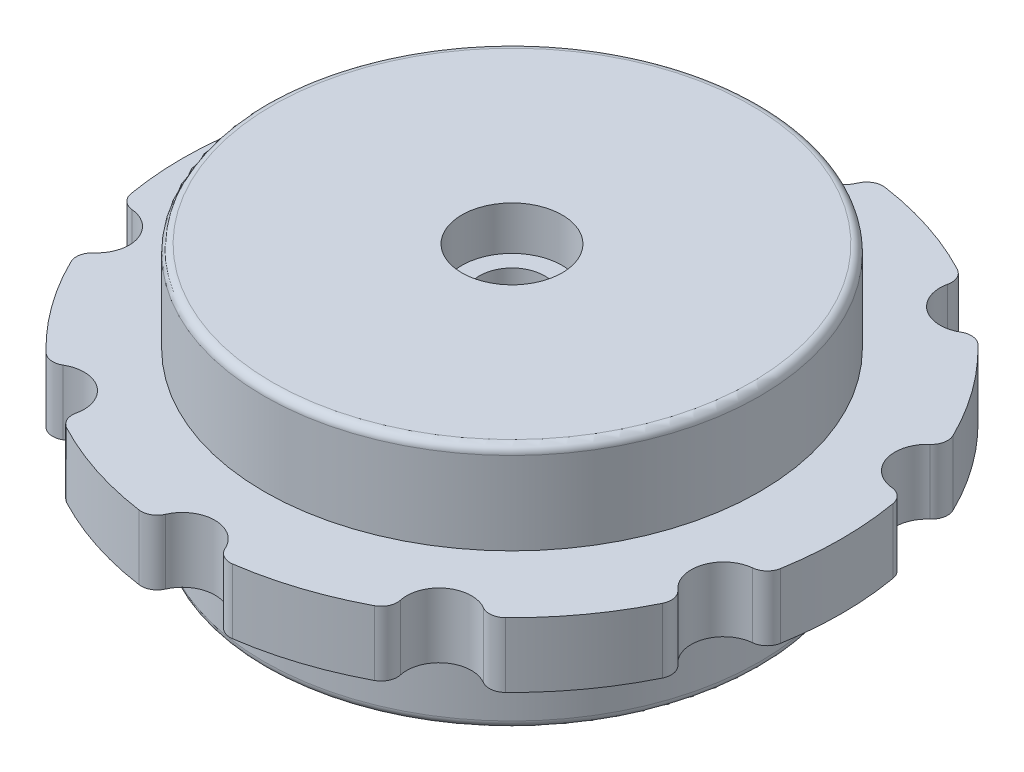
SolidWorks part; units mm, degrees
ref_plane "前视基准面" through (0, 0, 0) normal (0, 0, 1) x (1, 0, 0)
ref_plane "上视基准面" through (0, 0, 0) normal (0, 1, 0) x (1, 0, 0)
ref_plane "右视基准面" through (0, 0, 0) normal (1, 0, 0) x (0, 0, -1)
other "Configuration Table"
sketch "草图1" plane through (0, 0, 0) normal (0, 1, 0) x (1, 0, 0)
  circle A0 centre (0, 0) radius 15.3
  circle A1 centre (0, 0) radius 20.35
  circle A2 centre (0, 0) radius 13.7
  circle A3 centre (0, 20.35) radius 2
  dimension "D1" = 30.6
  dimension "D2" = 40.7
  dimension "D3" = 1.6
  dimension "D4" = 4
extrude "凸台-拉伸1" add sketch "草图1" along normal mid plane 15.2 contours A0 | A2
extrude "凸台-拉伸2" add sketch "草图1<3>" along normal mid plane 4 contours A1
sketch "草图1<3>" plane through (0, 0, 0) normal (0, 1, 0) x (1, 0, 0) same geometry as "草图1"
extrude "切除-拉伸1" cut sketch "草图1<4>" against normal through all both and the other way through all contours A3
sketch "草图1<4>" plane through (0, 0, 0) normal (0, 1, 0) x (1, 0, 0) same geometry as "草图1"
fillet "圆角1" radius 1 2 edges at (1.9976, 0, -20.2517) (-1.9976, 0, -20.2517)
pattern_circular "阵列(圆周)1" count 10 over 360 about axis through (0, 2, 0) along (0, -1, 0) of "切除-拉伸1", "圆角1"
fillet "圆角2" radius 0.5 2 edges at (0, -7.6, 15.3) (0, 7.6, 15.3)
extrude "凸台-拉伸3" add sketch "草图1<5>" along normal mid plane 7.8 contours A2
sketch "草图1<5>" plane through (0, 0, 0) normal (0, 1, 0) x (1, 0, 0) same geometry as "草图1"
extrude "凸台-拉伸5" add sketch "草图1<6>" along normal up to surface (7.6 mm away) from surface contours A2 up to face at (0, 7.6, 14.8) starting at face at (0, -7.6, 14.8)
sketch "草图1<6>" plane through (0, 0, 0) normal (0, 1, 0) x (1, 0, 0) same geometry as "草图1"
sketch "草图2" plane through (0, 2, 0) normal (0, 1, 0) x (1, 0, 0)
  line L0 (0, 20.35) -> (11.9614, 16.4635)
  line L1 (-11.9614, 16.4635) -> (0, 20.35)
  arc A0 (-1.834, 19.5523) -> (1.834, 19.5523) centre (0, 20.35) ccw construction
  arc A1 (10.0088, 16.8962) -> (12.9763, 14.7401) centre (11.9614, 16.4635) ccw construction
  arc A2 (-12.9763, 14.7401) -> (-10.0088, 16.8962) centre (-11.9614, 16.4635) ccw construction
  dimension "D1" = 12.577
  dimension "D2" = 12.577
sketch "草图4" plane through (0, -7.6, 0) normal (0, -1, 0) x (1, 0, 0)
  circle A0 centre (0, 0) radius 2
  circle A1 centre (0, 0) radius 3.1
  dimension "D1" = 4
  dimension "D2" = 6.2
extrude "切除-拉伸3" cut sketch "草图4" against normal through all contours A0
extrude "切除-拉伸4" cut sketch "草图4<3>" against normal blind 2.7 contours A1
sketch "草图4<3>" plane through (0, -7.6, 0) normal (0, -1, 0) x (1, 0, 0) same geometry as "草图4"
extrude "切除-拉伸5" cut sketch "草图4<4>" along normal blind 2.7 from surface contours A1 starting at face at (0, 7.6, -2)
sketch "草图4<4>" plane through (0, -7.6, 0) normal (0, -1, 0) x (1, 0, 0) same geometry as "草图4"
